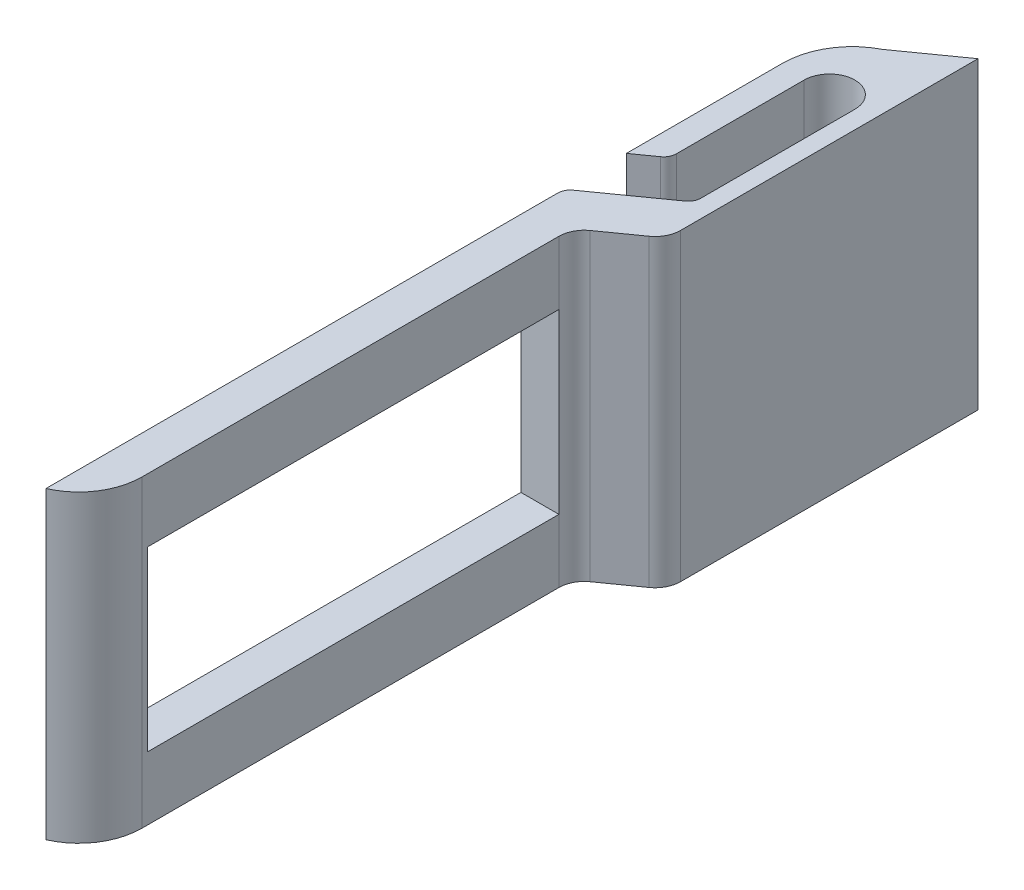
SolidWorks part; units mm, degrees
ref_plane "Front Plane" through (0, 0, 0) normal (0, 0, 1) x (1, 0, 0)
ref_plane "Top Plane" through (0, 0, 0) normal (0, 1, 0) x (1, 0, 0)
ref_plane "Right Plane" through (0, 0, 0) normal (1, 0, 0) x (0, 0, -1)
sketch "Sketch1" plane through (0, 0, 0) normal (0, 1, 0) x (1, 0, 0)
  line L0 (1.5, 36.5) -> (5.9, 39.6277)
  line L1 (-1.5, 36.5) -> (1.5, 36.5)
  line L2 (-1.5, 36.5) -> (-1.5, -26.5)
  line L4 (1.5, 11.9969) -> (1.5, -26.5)
  line L5 (-1.5, 36.5) -> (1.089, -26.5) construction
  line L6 (-1.089, -26.5) -> (1.5, 36.5) construction
  line L7 (5.9, 39.6277) -> (5.9, 15.1246)
  line L8 (5.9, 15.1246) -> (1.5, 11.9969)
  line L9 (1.5, -26.5) -> (-1.5, -26.5)
  point P0 (0, 0)
  dimension "D2" = 3
  dimension "D3" = 7.4
  dimension "D4" = 63
extrude "Boss-Extrude1" add sketch "Sketch1" along normal blind 24
sketch "Sketch2" plane through (0, 24, 0) normal (0, 1, 0) x (1, 0, 0)
  line L0 (-1.5, 14.384) -> (4.5, 18.6491)
  line L1 (-1.5, 36.5) -> (-1.5, -26.5) construction
  line L2 (1.5, 11.9969) -> (5.9, 15.1246) construction
  line L3 (-1.5, 14.384) -> (-1.5, 19.2916)
  line L4 (-1.5, 19.2916) -> (0.5, 20.7133)
  line L5 (0.5, 20.7133) -> (0.5, 31.3133)
  line L7 (4.5, 31.3133) -> (4.5, 18.6491)
  line L8 (4.5, 31.3133) -> (0.5, 31.3133) construction
  arc A0 (4.5, 31.3133) -> (0.5, 31.3133) centre (2.5, 31.3133) ccw
  dimension "D1" = 2
  dimension "D2" = 4
  dimension "D3" = 4
extrude "Cut-Extrude1" cut sketch "Sketch2" against normal blind 24
fillet "Fillet5" radius 1 3 edges at (-1.5, 12, -14.384) (4.5, 12, -18.6491) (0.5, 12, -20.7133)
fillet "Fillet6" radius 5.5 1 edges at (-1.5, 12, -36.5)
fillet "Fillet8" radius 2 2 edges at (1.5, 12, -11.9969) (5.9, 12, -15.1246)
sketch "Sketch3" plane through (1.5, 0, 0) normal (1, 0, 0) x (0, 0, -1)
  line L0 (10.9648, 19) -> (10.9648, 5)
  line L1 (10.9648, 19) -> (-21.5, 19)
  line L2 (10.9648, 5) -> (-21.5, 5)
  line L4 (10.9648, 0) -> (10.9648, 24) construction
  line L5 (-26.5, 0) -> (10.9648, 0) construction
  line L6 (-26.5, 24) -> (10.9648, 24) construction
  line L8 (-21.5, 19) -> (-21.5, 5)
  line L9 (-26.5, 24) -> (-26.5, 0) construction
  dimension "D1" = 5
  dimension "D2" = 5
  dimension "D3" = 5
extrude "Cut-Extrude2" cut sketch "Sketch3" against normal blind 10
fillet "Fillet9" radius 5 1 edges at (1.5, 12, 26.5)
